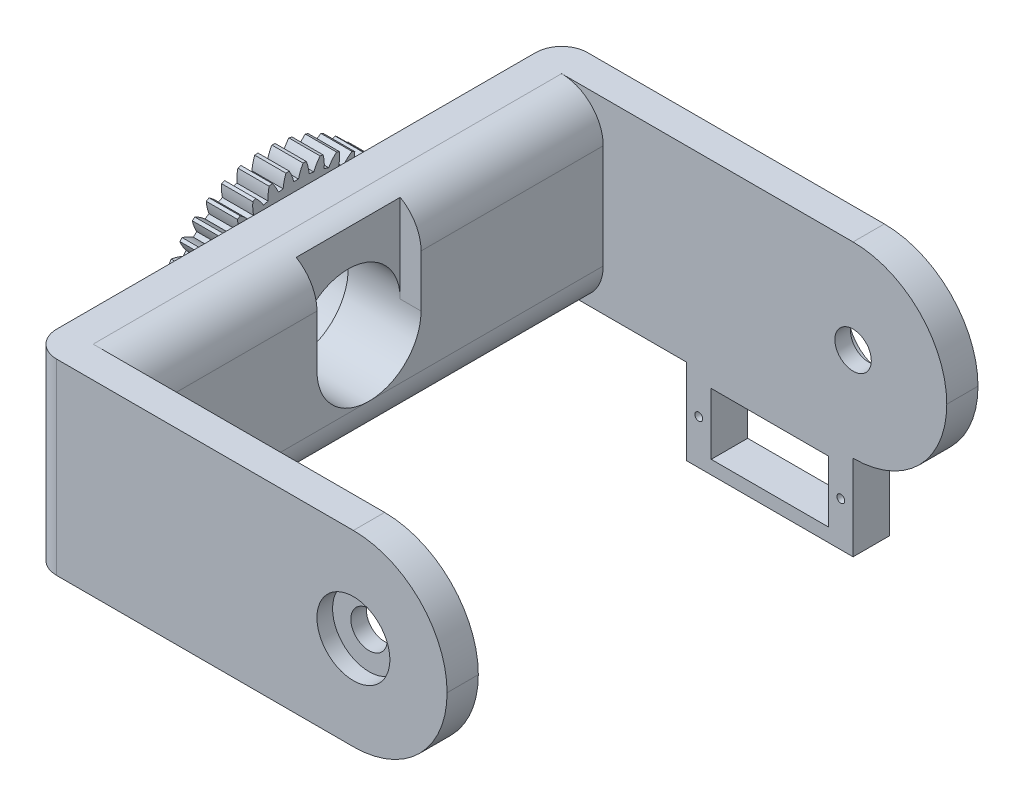
SolidWorks part; units mm, degrees
ref_plane "Plane1" through (0, 0, 0) normal (0, 0, 1) x (1, 0, 0)
ref_plane "Plane2" through (0, 0, 0) normal (0, 1, 0) x (1, 0, 0)
ref_plane "Plane3" through (0, 0, 0) normal (1, 0, 0) x (0, 0, -1)
other "Configuration Table"
sketch "HoldingSke" plane through (0, 0, 0) normal (0, 1, 0) x (1, 0, 0)
  line L0 (0, 0) -> (0.7431, -0.6691)
  line L1 (-15, 0) -> (100, 0) construction
  line L2 (0, 0) -> (-2.1039, 2.3779)
  line L3 (0, 0) -> (-11.863, 4.5341)
  line L4 (0, 0) -> (6.4178, 5.7786)
  line L5 (0, 0) -> (-46.8476, -17.4728)
  line L6 (0, 0) -> (-4.9738, -3.3558)
  line L7 (-2.1039, 2.3779) -> (8.6586, 51.2059)
  line L8 (-76.2, 54.61) -> (-76.1, 54.61)
  line L9 (-71.009, 38.7566) -> (-53.1078, 45.2721)
  line L10 (-76.2, 71.12) -> (104.1128, 71.12)
  line L11 (0, 0) -> (-6, 0)
  line L12 (-76.2, 101.6) -> (-76.162, 101.6)
  line L13 (24.9733, 27.94) -> (52.9518, 28.4284)
  line L14 (24.9733, 27.94) -> (24.9743, 27.94)
  line L15 (24.9733, 27.94) -> (100.4006, 29.5858)
  line L16 (-63.627, -1) -> (-12.827, -1)
  circle A0 centre (0, 0) radius 0.4
  circle A1 centre (0, 0) radius 19.749
  circle A2 centre (0, 0) radius 37.5
  circle A3 centre (0, 0) radius 0.4
  dimension "Num_teeth" = 42
  dimension "Pitch_radius" = 180.3128
  dimension "Width" = 6
  dimension "Thickness" = 6
sketch "BasProSke" plane through (0, 0, 0) normal (0, 1, 0) x (1, 0, 0)
  line L0 (-10, 0) -> (60, 0) construction
  line L1 (0, 0) -> (0, 22)
  line L2 (0, 0) -> (6, 0)
  line L3 (6, 0) -> (6, 22)
  line L4 (6, 22) -> (0, 22)
  dimension "Thickness" = 6
  dimension "Diameter" = 44
revolve "Base-Revolve" add sketch "BasProSke" angle 360 about L0
sketch "TooCutSke" plane through (0, 0, 0) normal (1, 0, 0) x (0, 0, -1)
  line L1 (0, 0) -> (0, 107) construction
  line L2 (0, 0) -> (-0.8517, 20.9827) construction
  line L3 (0, 0) -> (-3.1368, 41.858) construction
  line L4 (-0.8517, 20.9827) -> (-1.5684, 20.929) construction
  arc A0 (0.4461, 19.744) -> (-0.4461, 19.744) centre (0, 0) ccw
  arc A1 (1.3487, 21.9841) -> (-1.3487, 21.9841) centre (0, 0) ccw
  circle A2 centre (0, 0) radius 21 construction
  circle A3 centre (0, 0) radius 19.7335 construction
  arc A4 (-0.4461, 19.744) -> (-1.3487, 21.9841) centre (-8.6078, 17.7572) ccw
  arc A5 (1.3487, 21.9841) -> (0.4461, 19.744) centre (8.6078, 17.7572) ccw
extrude "ToothCut" cut sketch "TooCutSke" along normal through all
fillet "Breaks" [suppressed] radius 0.02 tangent propagation no
fillet "RootFillets" [suppressed] radius 0.251
pattern_circular "TeethCuts" count 42 every 8.571 about axis through (-10, 0, 0) along (1, 0, 0) of "ToothCut", "RootFillets", "Breaks"
sketch "HubNeaOneSke" plane through (0, 0, 0) normal (-1, 0, 0) x (0, 0, 1)
  circle A0 centre (0, 0) radius 19.749
  dimension "Diameter" = 39.498
extrude "HubNearOne" [suppressed] add sketch "HubNeaOneSke" along normal blind 44.0001
sketch "HubNeaBotSke" plane through (0, 0, 0) normal (-1, 0, 0) x (0, 0, 1)
  circle A0 centre (0, 0) radius 19.749
  dimension "Diameter" = 39.498
extrude "HubNearBoth" [suppressed] add sketch "HubNeaBotSke" along normal blind 22
ref_plane "FarPln" through (6, 0, 0) normal (1, 0, 0) x (0, 0, -1)
sketch "HubFarSke" plane through (6, 0, 0) normal (1, 0, 0) x (0, 0, -1)
  circle A0 centre (0, 0) radius 19.749
  dimension "Diameter" = 39.498
extrude "HubFar" [suppressed] add sketch "HubFarSke" along normal blind 22
sketch "BorSke" plane through (0, 0, 0) normal (1, 0, 0) x (0, 0, -1)
  circle A0 centre (0, 0) radius 0.4
  dimension "Diameter" = 0.8
extrude "Bore" cut sketch "BorSke" along normal mid plane 100.0001
sketch "KeySke" plane through (0, 0, 0) normal (1, 0, 0) x (0, 0, -1)
  line L0 (-0.05, 0) -> (-0.05, 0.5)
  line L1 (-0.05, 0.5) -> (0.05, 0.5)
  line L2 (0.05, 0.5) -> (0.05, 0)
  line L3 (0, 0) -> (0, 34) construction
  line L4 (-0.05, 0) -> (0.05, 0)
  dimension "Width" = 0.1
extrude "Keyway" [suppressed] cut sketch "KeySke" along normal mid plane 100.0001
pattern_circular "Keyway2" [suppressed] count 2 every 90 about axis through (-10, 0, 0) along (1, 0, 0)
sketch "Sketch1" plane through (6, 0, 0) normal (1, 0, 0) x (0, 0, -1)
  circle A0 centre (0, 0) radius 12.15
  dimension "D1" = 24.3
extrude "Cut-Extrude1" cut sketch "Sketch1" against normal through all
sketch "Sketch2" plane through (6, 0, 0) normal (1, 0, 0) x (0, 0, -1)
  line L1 (-51, -18) -> (51, -18)
  line L2 (-51, -18) -> (-51, 18)
  line L3 (-51, 18) -> (51, 18)
  line L4 (51, -18) -> (51, 18)
  line L5 (-51, -18) -> (51, 18) construction
  line L6 (-51, 18) -> (51, -18) construction
  point P0 (0, 0)
  dimension "D1" = 36
  dimension "D2" = 102
extrude "Boss-Extrude1" add sketch "Sketch2" along normal blind 10
sketch "Sketch3" plane through (16, 0, 0) normal (1, 0, 0) x (0, 0, -1)
  line L0 (0, 18) -> (0, -18) construction
  line L1 (8.1684, 18) -> (-8.1684, 18) construction
  line L2 (-8.1684, -18) -> (8.1684, -18) construction
  line L3 (-51, -18) -> (51, -18) construction
  line L4 (-51, 18) -> (-45, 18)
  line L5 (-51, 18) -> (-51, -18)
  line L6 (-51, -18) -> (-45, -18)
  line L7 (-45, 18) -> (-45, -18)
  line L8 (51, -18) -> (45, -18)
  line L9 (45, 18) -> (45, -18)
  line L10 (51, 18) -> (45, 18)
  line L11 (51, 18) -> (51, -18)
  dimension "D1" = 6
extrude "Boss-Extrude2" add sketch "Sketch3" along normal blind 70
fillet "Fillet1" radius 18 4 edges at (86, -18, -48) (86, 18, -48) (86, 18, 48) (86, -18, 48)
fillet "Fillet2" radius 5 2 edges at (6, 0, -51) (6, 0, 51)
sketch "Sketch4" plane through (0, 0, 51) normal (0, 0, 1) x (1, 0, 0)
  line L0 (68, 18) -> (68, -18) construction
  circle A0 centre (68, 0) radius 3.5
  dimension "D1" = 7
extrude "Cut-Extrude2" cut sketch "Sketch4" against normal through all both and the other way through all
sketch "Sketch5" plane through (0, 0, 51) normal (0, 0, 1) x (1, 0, 0)
  circle A0 centre (68, 0) radius 7
  dimension "D1" = 14
extrude "Cut-Extrude3" cut sketch "Sketch5" against normal blind 3 and the other way through all
sketch "Sketch6" plane through (0, 0, -51) normal (0, 0, -1) x (-1, 0, 0)
  circle A0 centre (-68, 0) radius 7
  dimension "D1" = 14
extrude "Cut-Extrude4" cut sketch "Sketch6" against normal blind 3
sketch "Sketch7" plane through (6, 0, 0) normal (-1, 0, 0) x (0, 0, 1)
  circle A0 centre (0, 0) radius 10
  dimension "D1" = 20
extrude "Cut-Extrude5" cut sketch "Sketch7" against normal through all
sketch "Sketch8" plane through (16, 0, 0) normal (1, 0, 0) x (0, 0, -1)
  line L0 (-45, 18) -> (-45, -18)
  line L1 (-45, -18) -> (45, -18)
  line L2 (45, -18) -> (45, 18)
  line L3 (45, 18) -> (10, 18)
  line L4 (45, 18) -> (-45, 18) construction
  line L6 (-10, 0) -> (-10, 18)
  line L7 (-10, 18) -> (-45, 18)
  line L8 (10, 18) -> (10, 0)
  line L9 (0, 0) -> (0, 18) construction
  line L10 (8.1684, 18) -> (-8.1684, 18) construction
  circle A0 centre (0, 0) radius 10 construction
  arc A1 (-10, 0) -> (10, 0) centre (0, 0) ccw
  dimension "D1" = 10
extrude "Boss-Extrude3" add sketch "Sketch8" along normal blind 4
fillet "Fillet3" radius 8 2 edges at (20, 18, 27.5) (20, -18, 0)
sketch "Sketch9" plane through (0, 0, -51) normal (0, 0, -1) x (-1, 0, 0)
  line L5 (-68, 0) -> (-68, -18) construction
  line L6 (-68, -34.3955) -> (-36, -34.3955)
  line L7 (-68, -34.3955) -> (-68, -17.3955)
  line L8 (-68, -17.3955) -> (-36, -17.3955)
  line L9 (-36, -34.3955) -> (-36, -17.3955)
  line L10 (-68, -34.3955) -> (-36, -17.3955) construction
  line L11 (-68, -17.3955) -> (-36, -34.3955) construction
  line L12 (-68, -18) -> (-11, -18) construction
  line L13 (-36, -25.8955) -> (-68, -25.8955) construction
  line L14 (-63.25, -31.7955) -> (-40.75, -31.7955) construction
  line L15 (-63.25, -31.7955) -> (-63.25, -19.9955) construction
  line L16 (-63.25, -19.9955) -> (-40.75, -19.9955) construction
  line L17 (-40.75, -31.7955) -> (-40.75, -19.9955) construction
  line L18 (-63.25, -31.7955) -> (-40.75, -19.9955) construction
  line L19 (-63.25, -19.9955) -> (-40.75, -31.7955) construction
  line L20 (-57.35, -25.8955) -> (-68, 0) construction
  circle A0 centre (-57.35, -25.8955) radius 5.9 construction
  point P0 (-52, -25.8955)
  point P10 (-52, -25.8955)
  dimension "D1" = 17
  dimension "D2" = 32
  dimension "D3" = 11.8
  dimension "D4" = 22.5
  dimension "D5" = 5.9
  dimension "D6" = 28
extrude "Boss-Extrude4" add sketch "Sketch9" along normal blind 1 and the other way blind 6
sketch "Sketch10" plane through (0, 0, -52) normal (0, 0, -1) x (-1, 0, 0)
  line L0 (-68, -25.8955) -> (-36, -25.8955) construction
  line L1 (-68, -17.3955) -> (-68, -34.3955) construction
  line L2 (-36, -34.3955) -> (-36, -17.3955) construction
  line L3 (-52, -17.3955) -> (-52, -34.3955) construction
  line L4 (-36, -17.3955) -> (-68, -17.3955) construction
  line L5 (-68, -34.3955) -> (-36, -34.3955) construction
  line L7 (-63.25, -31.7955) -> (-40.75, -31.7955)
  line L8 (-63.25, -31.7955) -> (-63.25, -19.9955)
  line L9 (-63.25, -19.9955) -> (-40.75, -19.9955)
  line L10 (-40.75, -31.7955) -> (-40.75, -19.9955)
  line L11 (-63.25, -31.7955) -> (-40.75, -19.9955) construction
  line L12 (-63.25, -19.9955) -> (-40.75, -31.7955) construction
  circle A0 centre (-65.65, -25.8955) radius 0.75
  circle A1 centre (-38.35, -25.8955) radius 0.75
  point P12 (-52, -25.8955)
  dimension "D4" = 1.5
  dimension "D1" = 22.5
  dimension "D2" = 11.8
  dimension "D3" = 13.65
extrude "Cut-Extrude6" cut sketch "Sketch10" against normal up to next
equation "' \"Module@HoldingSke\" = 6.35"
equation "' \"Num_teeth@HoldingSke\" = 12"
equation "' \"Ap@HoldingSke\" =  20"
equation "' \"Ap@HoldingSke\" = 20"
equation "' \"Width@HoldingSke\" = 0.5 * 25.4"
equation "' \"Hub_dia@HoldingSke\"= 1 * 25.4"
equation "' \"Hub_dia@HoldingSke\" = 1 * 25.4"
equation "' \"Overall_len@HoldingSke\" = 1.0 * 25.4"
equation "' \"Bore@HoldingSke\" = 0.75 * 25.4"
equation "' \"T_dim@HoldingSke\" = 0.1 * 25.4"
equation "' \"Width@KeySke\" = 0.25 * 25.4"
equation "' \"Show_teeth@HoldingSke\" = 13"
equation "' \"Backlash@HoldingSke\" = 0.009 * 25.4"
equation "' \"Addendum_fac@HoldingSke\" = 1.0"
equation "' \"Dedendum_fac@HoldingSke\" = 1.25"
equation "' \"Dedendum_add@HoldingSke\" = 0.00005 * 25.4"
equation "' \"Clearance_fac@HoldingSke\" = 0.25"
equation "\"Pitch@HoldingSke\" = 1 / \"Module@HoldingSke\""
equation "\"Overcut_dia@TooCutSke\" = (\"Num_teeth@HoldingSke\" + 2 * \"Addendum_fac@HoldingSke\") / \"Pitch@HoldingSke\" + 0.002 * 25.4"
equation "\"Pitch_dia@TooCutSke\" = \"Num_teeth@HoldingSke\" / \"Pitch@HoldingSke\""
equation "\"Base_dia@TooCutSke\" = \"Num_teeth@HoldingSke\" / \"Pitch@HoldingSke\" * cos((\"Ap@HoldingSke\"  * 3.14159265 / 180))"
equation "\"Root_dia@TooCutSke\" = (\"Num_teeth@HoldingSke\" + 2) / \"Pitch@HoldingSke\" - 2 * (\"Addendum_fac@HoldingSke\" + \"Dedendum_fac@HoldingSke\") / \"Pitch@HoldingSke\" - \"Dedendum_add@HoldingSke\" * 2"
equation "\"Half_ang@TooCutSke\" = 180 / \"Num_teeth@HoldingSke\""
equation "\"Half_CT@TooCutSke\" = \"Num_teeth@HoldingSke\" / \"Pitch@HoldingSke\" * sin((3.14159265 / 2 / \"Num_teeth@HoldingSke\")) / 2 - 7 * \"Backlash@HoldingSke\" / 4"
equation "\"Flank_rad@TooCutSke\" = \"Num_teeth@HoldingSke\" / \"Pitch@HoldingSke\" / 5"
equation "\"Radius@RootFillets\" = \"Clearance_fac@HoldingSke\" / \"Pitch@HoldingSke\" + \"Dedendum_add@HoldingSke\""
equation "\"Break_rad@Breaks\" = 0.02 / \"Pitch@HoldingSke\""
equation "\"Thickness@HoldingSke\" = \"Width@HoldingSke\""
equation "\"OAL@HoldingSke\" = \"Thickness@HoldingSke\""
equation "\"MHD@HoldingSke\" = (\"Num_teeth@HoldingSke\" + 2) / \"Pitch@HoldingSke\" - 2 * (\"Addendum_fac@HoldingSke\" + \"Dedendum_fac@HoldingSke\")  / \"Pitch@HoldingSke\" - \"Dedendum_add@HoldingSke\" * 2"
equation "\"MBD@HoldingSke\" = (\"Num_teeth@HoldingSke\" + 2) / \"Pitch@HoldingSke\" - 2 * (\"Addendum_fac@HoldingSke\" + \"Dedendum_fac@HoldingSke\")  / \"Pitch@HoldingSke\" - \"Dedendum_add@HoldingSke\" * 2 - 0.002 * 25.4"
equation "\"MHD@HoldingSke\" = ((sgn( \"MHD@HoldingSke\" - \"Hub_dia@HoldingSke\" )-1)*( \"MHD@HoldingSke\" - \"Hub_dia@HoldingSke\" ))/-2+ \"Hub_dia@HoldingSke\""
equation "\"MBD@HoldingSke\" = ((sgn( \"MBD@HoldingSke\" - \"Bore@HoldingSke\" )-1)*( \"MBD@HoldingSke\" - \"Bore@HoldingSke\" ))/-2+ \"Bore@HoldingSke\""
equation "\"OAL@HoldingSke\" = ((sgn( \"OAL@HoldingSke\" - \"Overall_len@HoldingSke\" )+1)*( \"OAL@HoldingSke\" - \"Overall_len@HoldingSke\" ))/2 + \"Overall_len@HoldingSke\" + 0.000002 * 25.4"
equation "\"Num_teeth@TeethCuts\" = int( \"Show_teeth@HoldingSke\" ) + 1"
equation "\"Num_teeth@TeethCuts\" = ((sgn( \"Num_teeth@TeethCuts\" - \"Num_teeth@HoldingSke\" )-1)*( \"Num_teeth@TeethCuts\" - \"Num_teeth@HoldingSke\" ))/-2+ \"Num_teeth@HoldingSke\""
equation "\"Num_teeth@TeethCuts\" = ((sgn( \"Num_teeth@TeethCuts\" - 2.0)+1)*( \"Num_teeth@TeethCuts\" - 2.0))/2 +2.0"
equation "\"Angle@TeethCuts\" = 360.0 / \"Num_teeth@HoldingSke\""
equation "\"Diameter@BasProSke\" = (\"Num_teeth@HoldingSke\" + 2 * \"Addendum_fac@HoldingSke\") / \"Pitch@HoldingSke\""
equation "\"Thickness@BasProSke\"  = \"Thickness@HoldingSke\""
equation "' \"Fillet_rad@BasProSke\" =  \"Thickness@HoldingSke\" * 0.05"
equation "' \"Fillet_rad@BasProSke\" = \"Thickness@HoldingSke\" * 0.05"
equation "\"MHD@HoldingSke\" = ((sgn( \"MHD@HoldingSke\" - \"Root_dia@TooCutSke\" )-1)*( \"MHD@HoldingSke\" - \"Root_dia@TooCutSke\" ))/-2+ \"Root_dia@TooCutSke\""
equation "\"Diameter@HubNeaOneSke\" = \"MHD@HoldingSke\""
equation "\"Length@HubNearOne\" = \"OAL@HoldingSke\" - \"Thickness@BasProSke\""
equation "\"Diameter@HubNeaBotSke\" = \"MHD@HoldingSke\""
equation "\"Length@HubNearBoth\" = ( \"OAL@HoldingSke\" - \"Thickness@BasProSke\" ) / 2.0"
equation "\"Thickness@FarPln\" = \"Thickness@BasProSke\""
equation "\"Diameter@HubFarSke\" = \"MHD@HoldingSke\""
equation "\"Length@HubFar\" = ( \"OAL@HoldingSke\" - \"Thickness@BasProSke\" ) / 2.0"
equation "\"Diameter@BorSke\" = \"MBD@HoldingSke\""
equation "\"D1@Bore\" = \"OAL@HoldingSke\" * 2.0"
equation "\"D1@Keyway\" = \"OAL@HoldingSke\" * 2.0"
equation "\"Offset@KeySke\" = \"T_dim@HoldingSke\" + \"MBD@HoldingSke\" / 2.0"
